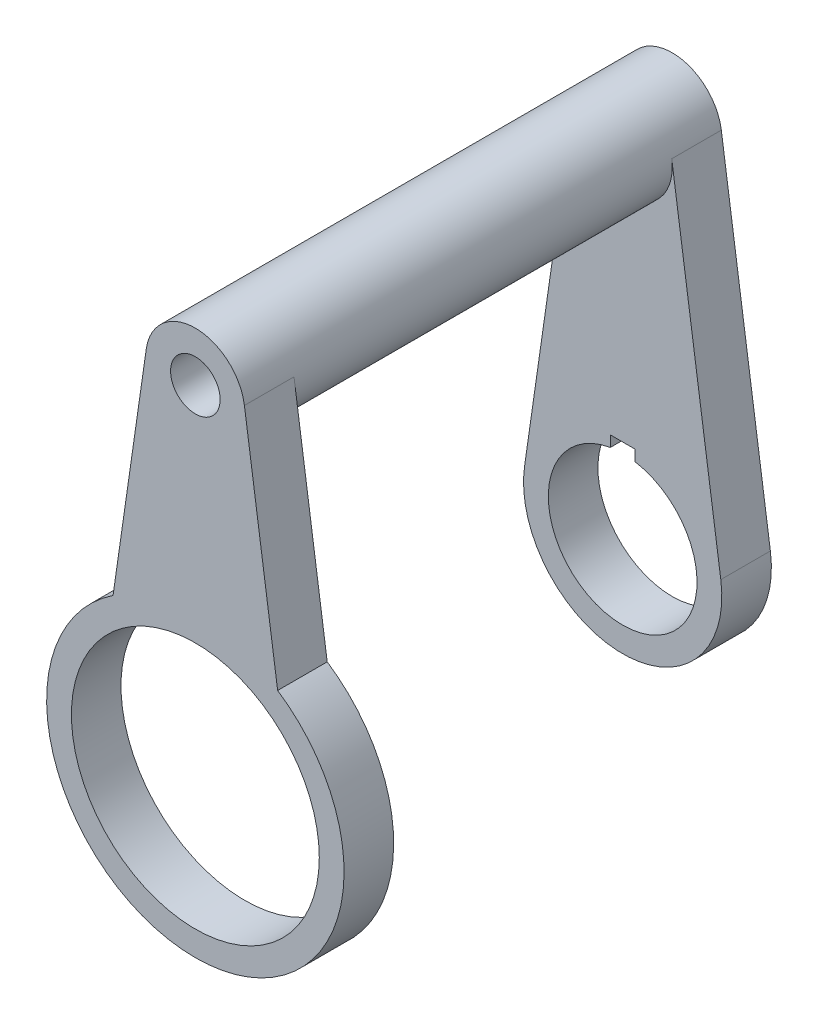
SolidWorks part; units mm, degrees
ref_plane "Front Plane" through (0, 0, 0) normal (0, 0, 1) x (1, 0, 0)
ref_plane "Top Plane" through (0, 0, 0) normal (0, 1, 0) x (1, 0, 0)
ref_plane "Right Plane" through (0, 0, 0) normal (1, 0, 0) x (0, 0, -1)
sketch "Sketch2" plane through (0, 0, 0) normal (0, 0, 1) x (1, 0, 0)
  line L0 (-19.7949, 2.8571) -> (-9.8974, 71.4286)
  line L1 (9.8974, 71.4286) -> (19.7949, 2.8571)
  line L2 (-2.5, 14.7902) -> (-2.5, 17)
  line L3 (-2.5, 17) -> (2.5, 17)
  line L4 (2.5, 17) -> (2.5, 14.7902)
  arc A0 (-19.7949, 2.8571) -> (19.7949, 2.8571) centre (0, 0) ccw
  arc A1 (-2.5, 14.7902) -> (2.5, 14.7902) centre (0, 0) ccw
  arc A2 (9.8974, 71.4286) -> (-9.8974, 71.4286) centre (0, 70) ccw
  circle A3 centre (0, 70) radius 5
  point P12 (0, 17)
  dimension "D1" = 30
  dimension "D2" = 40
  dimension "D3" = 10
  dimension "D4" = 20
  dimension "D5" = 70
  dimension "D6" = 17
  dimension "D7" = 5
extrude "Boss-Extrude1" add sketch "Sketch2" along normal blind 10
sketch "Sketch3" plane through (0, 0, 10) normal (0, 0, 1) x (1, 0, 0)
  circle A0 centre (0, 70) radius 10
  arc A1 (9.8974, 71.4286) -> (-9.8974, 71.4286) centre (0, 70) ccw construction
  circle A2 centre (0, 70) radius 5
  circle A3 centre (0, 70) radius 5 construction
extrude "Boss-Extrude2" add sketch "Sketch3" along normal blind 76.2
extrude "Boss-Extrude3" add sketch "Sketch2<2>" along normal blind 10 from surface starting at face at (10, 70, 86.2)
sketch "Sketch2<2>" plane through (0, 0, 0) normal (0, 0, 1) x (1, 0, 0) same geometry as "Sketch2"
sketch "Sketch5" plane through (0, 0, 96.2) normal (0, 0, 1) x (1, 0, 0)
  circle A0 centre (0, 0) radius 30
  dimension "D1" = 60
extrude "Boss-Extrude4" add sketch "Sketch5" against normal up to surface (10 mm away) up to face at (0, 8.4475, 86.2)
sketch "Sketch6" plane through (0, 0, 96.2) normal (0, 0, 1) x (1, 0, 0)
  circle A0 centre (0, 0) radius 25
  dimension "D1" = 50
extrude "Cut-Extrude1" cut sketch "Sketch6" against normal up to surface (10 mm away) contours A0 up to face at (0, 31.6043, 86.2)
